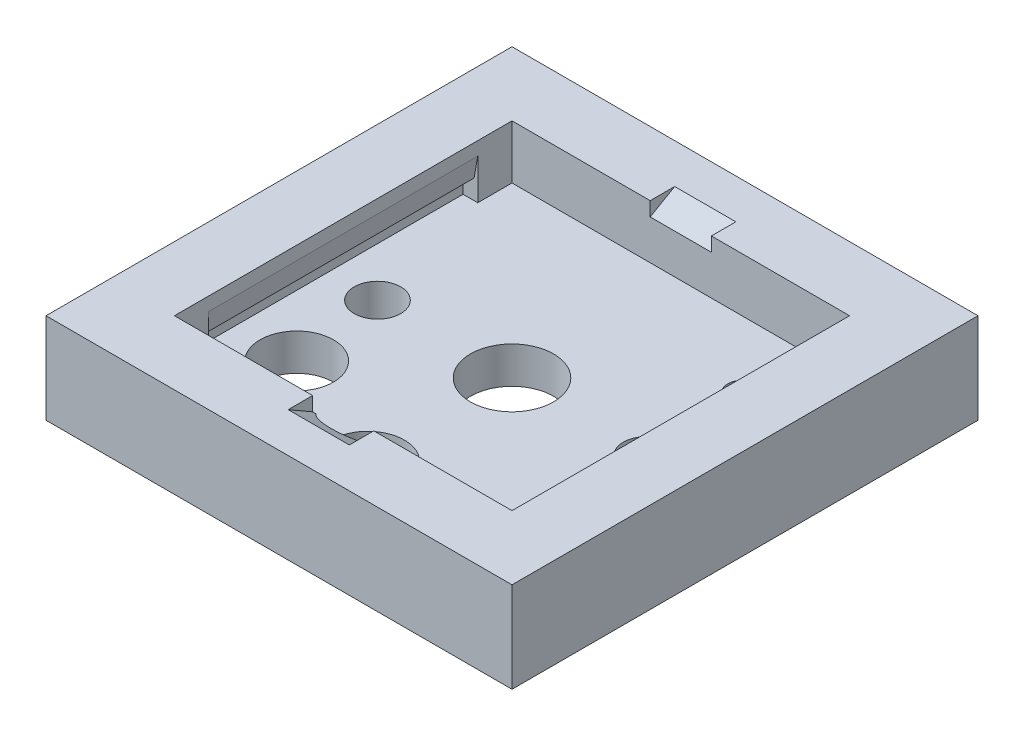
SolidWorks part; units mm, degrees
other "single-1350"
ref_plane "Front Plane" through (0, 0, 0) normal (0, 0, 1) x (1, 0, 0)
ref_plane "Top Plane" through (0, 0, 0) normal (0, 1, 0) x (1, 0, 0)
ref_plane "Right Plane" through (0, 0, 0) normal (1, 0, 0) x (0, 0, -1)
sketch "Sketch1" plane through (0, 0, 0) normal (0, 1, 0) x (1, 0, 0)
  line L0 (-6.9, 6.9) -> (6.9, 6.9)
  line L1 (6.9, 6.9) -> (6.9, -6.9)
  line L2 (6.9, -6.9) -> (1.118, -6.9)
  line L3 (-6.9, -6.9) -> (-6.9, 6.9)
  line L4 (13.0003, 0) -> (-13.0003, 0) construction
  line L5 (0, 13.0493) -> (0, -13.0493) construction
  line L6 (-1.118, -6.9) -> (-6.9, -6.9)
  line L8 (-9.525, -9.525) -> (9.525, -9.525)
  line L9 (-9.525, -9.525) -> (-9.525, 9.525)
  line L10 (-9.525, 9.525) -> (9.525, 9.525)
  line L11 (9.525, -9.525) -> (9.525, 9.525)
  line L12 (-9.525, -9.525) -> (9.525, 9.525) construction
  line L13 (-9.525, 9.525) -> (9.525, -9.525) construction
  circle A0 centre (0, 0) radius 1.7
  circle A1 centre (-5.5, 0) radius 0.95
  circle A2 centre (5.5, 0) radius 0.95
  circle A3 centre (-5, -3.8) radius 1.5
  circle A4 centre (0, -5.9) radius 1.5
  circle A5 centre (5.22, 4.2) radius 0.6
  point P20 (0, 0)
  point P23 (0, 0)
  dimension "D1" = 11
  dimension "D2" = 1.9
  dimension "D3" = 3
  dimension "D5" = 3.4
  dimension "D8" = 1.2
  dimension "D13" = 6.9
  dimension "D16" = 19.05
  dimension "D4" = 5
  dimension "D6" = 5.9
  dimension "D7" = 4.2
  dimension "D9" = 13.8
  dimension "D10" = 5.22
  dimension "D11" = 3.8
  dimension "D12" = 6.9
  dimension "D14" = 5.5
  dimension "D15" = 19.05
extrude "Boss-Extrude1" add sketch "Sketch1" along normal blind 3.7 contours L8 L11 L10 L9 A4 L6 L3 L0 L1 L2 | A4 L2 L1 L0 L3 L6 A5 A0 A1 A2 A3 region at (0, 0, -6.7048) region at (-9.2556, 0, 0)
extrude "Cut-Extrude1" cut sketch "Sketch1<3>" against normal blind 2.2 from surface contours A4 L2 L1 L0 L3 L6 A5 A0 A1 A2 A3 region at (0, 0, -6.7048) starting at face at (0, 3.7, 7.4)
sketch "Sketch1<3>" plane through (0, 0, 0) normal (0, 1, 0) x (1, 0, 0) same geometry as "Sketch1"
sketch "Sketch2" plane through (0, 0, 0) normal (1, 0, 0) x (0, 0, -1)
  line L0 (-7.9, 3.7) -> (-6.9, 3.7)
  line L1 (-6.9, 3.7) -> (-6.9, 3.1226)
  line L2 (-6.9, 3.1226) -> (-7.9, 3.7)
  line L3 (-6.9, 1.5) -> (-6.9, 3.7) construction
  dimension "D1" = 150
  dimension "D2" = 1
extrude "Cut-Extrude2" cut sketch "Sketch2" against normal mid plane 2.5
mirror "Mirror1" about plane through (0, 0, 0) normal (0, 0, 1) of "Cut-Extrude2"
sketch "Sketch4" plane through (0, 0, 0) normal (0, 0, 1) x (1, 0, 0)
  line L2 (-6.9, 3.1507) -> (-6.9, 1.5)
  line L3 (-6.9, 1.5) -> (-7.5, 1.5)
  line L4 (-7.5, 2.3) -> (-7.5, 1.5)
  line L5 (-6.9, 3.7) -> (-7.5, 1.5) construction
  line L10 (-7.5, 2.3) -> (-7.05, 2.3)
  line L11 (-7.05, 2.3) -> (-6.9, 3.1507)
  line L12 (-6.9, 3.7) -> (-6.9, 3.1507) construction
  dimension "D1" = 1.4
  dimension "D2" = 0.6
  dimension "D4" = 10
  dimension "D5" = 0.45
extrude "Cut-Extrude3" cut sketch "Sketch4" against normal mid plane 11
mirror "Mirror2" about plane through (0, 0, 0) normal (1, 0, 0) of "Cut-Extrude3"
equation "\"key_spacing\"= 19.05mm"
